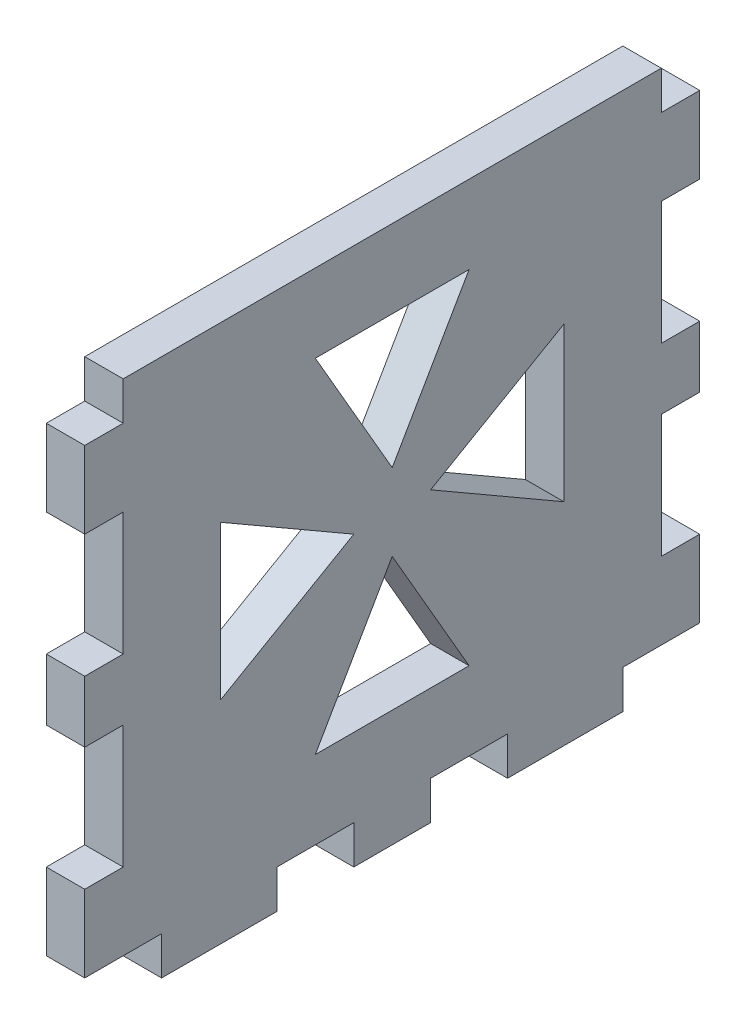
SolidWorks part; units mm, degrees
material "Pine"
ref_plane "Front Plane" through (0, 0, 0) normal (0, 0, 1) x (1, 0, 0)
ref_plane "Top Plane" through (0, 0, 0) normal (0, 1, 0) x (1, 0, 0)
ref_plane "Right Plane" through (0, 0, 0) normal (1, 0, 0) x (0, 0, -1)
sketch "Sketch1" plane through (0, 0, 0) normal (1, 0, 0) x (0, 0, -1)
  line L0 (50.8, 0) -> (50.8, 88.9) construction
  line L1 (0, 0) -> (101.6, 0)
  line L2 (0, 0) -> (0, 88.9)
  line L3 (0, 88.9) -> (101.6, 88.9)
  line L4 (101.6, 0) -> (101.6, 88.9)
  line L5 (0, 0) -> (6.35, 0)
  line L6 (0, 0) -> (0, 6.35)
  line L7 (0, 6.35) -> (6.35, 6.35)
  line L8 (6.35, 0) -> (6.35, 6.35)
  line L9 (101.6, 0) -> (95.25, 0)
  line L10 (101.6, 0) -> (101.6, 6.35)
  line L11 (101.6, 6.35) -> (95.25, 6.35)
  line L12 (95.25, 0) -> (95.25, 6.35)
  line L13 (0, 88.9) -> (6.35, 88.9)
  line L14 (0, 88.9) -> (0, 82.55)
  line L15 (0, 82.55) -> (6.35, 82.55)
  line L16 (6.35, 88.9) -> (6.35, 82.55)
  line L17 (101.6, 88.9) -> (95.25, 88.9)
  line L18 (101.6, 88.9) -> (101.6, 82.55)
  line L19 (101.6, 82.55) -> (95.25, 82.55)
  line L20 (95.25, 88.9) -> (95.25, 82.55)
  line L21 (101.6, 69.85) -> (95.25, 69.85)
  line L22 (101.6, 69.85) -> (101.6, 49.53)
  line L23 (101.6, 49.53) -> (95.25, 49.53)
  line L24 (95.25, 69.85) -> (95.25, 49.53)
  line L25 (101.6, 19.05) -> (95.25, 19.05)
  line L26 (101.6, 19.05) -> (101.6, 39.37)
  line L27 (101.6, 39.37) -> (95.25, 39.37)
  line L28 (95.25, 19.05) -> (95.25, 39.37)
  line L29 (0, 39.37) -> (6.35, 39.37)
  line L30 (6.35, 19.05) -> (6.35, 39.37)
  line L31 (0, 19.05) -> (6.35, 19.05)
  line L32 (0, 19.05) -> (0, 39.37)
  line L33 (0, 49.53) -> (6.35, 49.53)
  line L34 (6.35, 69.85) -> (6.35, 49.53)
  line L35 (0, 69.85) -> (6.35, 69.85)
  line L36 (0, 69.85) -> (0, 49.53)
  line L37 (6.35, 6.35) -> (95.25, 6.35)
  line L39 (12.7, 6.35) -> (31.75, 6.35)
  line L40 (12.7, 6.35) -> (12.7, 0)
  line L41 (12.7, 0) -> (31.75, 0)
  line L42 (31.75, 6.35) -> (31.75, 0)
  line L43 (88.9, 6.35) -> (69.85, 6.35)
  line L44 (88.9, 6.35) -> (88.9, 0)
  line L45 (88.9, 0) -> (69.85, 0)
  line L46 (69.85, 6.35) -> (69.85, 0)
  line L47 (57.15, 6.35) -> (44.45, 6.35)
  line L48 (57.15, 6.35) -> (57.15, 0)
  line L49 (57.15, 0) -> (44.45, 0)
  line L50 (44.45, 6.35) -> (44.45, 0)
  point P25 (98.425, 69.85)
  point P48 (31.75, 3.175)
  dimension "D1" = 101.6
  dimension "D2" = 88.9
  dimension "D3" = 6.35
  dimension "D4" = 6.35
  dimension "D5" = 6.35
  dimension "D6" = 6.35
  dimension "D7" = 6.35
  dimension "D8" = 6.35
  dimension "D9" = 6.35
  dimension "D10" = 6.35
  dimension "D11" = 12.7
  dimension "D12" = 12.7
  dimension "D13" = 20.32
  dimension "D14" = 20.32
  dimension "D15" = 12.7
  dimension "D16" = 12.7
  dimension "D17" = 12.7
  dimension "D18" = 12.7
  dimension "D19" = 12.7
  dimension "D20" = 19.05
extrude "Boss-Extrude1" add sketch "Sketch1" along normal blind 6.35 contours L1 L0 L3 L16 L15 L2 L35 L34 L33 L29 L30 L31 L7 L8 | L0 L1 L12 L11 L4 L25 L28 L27 L23 L24 L21 L19 L20 L3 | L40 L39 L42 L41 | L48 L47 L50 L49 | L44 L43 L46 L45 region at (0, 47.4409, -50.8)
sketch "Sketch2" plane through (6.35, 0, 0) normal (1, 0, 0) x (0, 0, -1)
  line L0 (50.8, 88.9) -> (50.8, 0) construction
  line L1 (44.45, 47.625) -> (22.453, 60.325)
  line L2 (22.453, 60.325) -> (22.453, 34.925)
  line L3 (22.453, 34.925) -> (44.45, 47.625)
  line L4 (6.35, 88.9) -> (95.25, 88.9) construction
  line L6 (50.8, 53.975) -> (63.5, 75.972)
  line L7 (101.6, 39.37) -> (101.6, 49.53) construction
  line L8 (101.6, 47.625) -> (0, 47.625) construction
  line L9 (0, 39.37) -> (0, 49.53) construction
  line L10 (63.5, 75.972) -> (38.1, 75.972)
  line L11 (38.1, 75.972) -> (50.8, 53.975)
  line L12 (57.15, 47.625) -> (79.147, 34.925)
  line L13 (79.147, 34.925) -> (79.147, 60.325)
  line L14 (79.147, 60.325) -> (57.15, 47.625)
  line L15 (50.8, 41.275) -> (38.1, 19.278)
  line L16 (38.1, 19.278) -> (63.5, 19.278)
  line L17 (63.5, 19.278) -> (50.8, 41.275)
  line L18 (57.15, 0) -> (44.45, 0) construction
  circle A0 centre (29.7853, 47.625) radius 7.3323 construction
  point P10 (50.8, 0)
  point P15 (50.8, 6.35)
  point P19 (0, 0)
  point P20 (50.8, 47.625)
  point P29 (50.8, 47.625)
  point P30 (0, 0)
  dimension "D1" = 6.35
  dimension "=" = 41.275
  dimension "D2" = 4
  dimension "D3" = 25.4
extrude "Cut-Extrude1" cut sketch "Sketch2" against normal up to surface (6.35 mm away) up to face at (0, 35.2778, -50.8)
